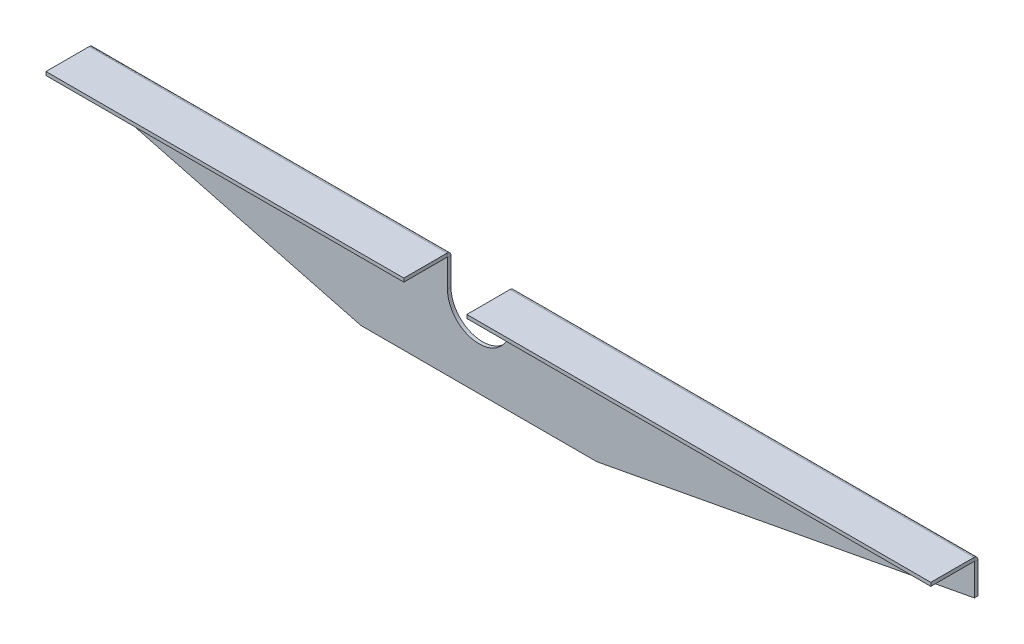
SolidWorks part; units mm, degrees
note: The reader was unsure of these and kept them because the rebuilt part matched: flange length of "Edge-Flange1".
material "Galvanized Steel"
ref_plane "Front Plane" through (0, 0, 0) normal (0, 0, 1) x (1, 0, 0)
ref_plane "Top Plane" through (0, 0, 0) normal (0, 1, 0) x (1, 0, 0)
ref_plane "Right Plane" through (0, 0, 0) normal (1, 0, 0) x (0, 0, -1)
sketch "Sketch1" plane through (0, 0, 0) normal (0, 0, 1) x (1, 0, 0)
  line L0 (13.35, 0) -> (13.35, 13.35)
  line L1 (13.35, 13.35) -> (210, 13.35)
  line L2 (210, 13.35) -> (210, -1.65)
  line L3 (210, -1.65) -> (50, -31.65)
  line L4 (50, -31.65) -> (-50, -31.65)
  line L5 (-50, -31.65) -> (-165, -1.65)
  line L6 (-165, -1.65) -> (-165, 13.35)
  line L7 (-165, 13.35) -> (-13.35, 13.35)
  line L8 (-13.35, 13.35) -> (-13.35, 0)
  arc A0 (-13.35, 0) -> (13.35, 0) centre (0, 0) ccw
  point P1 (0, -31.65)
  dimension "D1" = 26.7
  dimension "D2" = 100
  dimension "D3" = 0
  dimension "D4" = 15
  dimension "D5" = 15
  dimension "D6" = 165
  dimension "D7" = 210
  dimension "D8" = 45
base flange "Base-Flange1" sketch "Sketch1" thickness 1.5 reverse thickness direction no parameters "D1"=0.2
edge flange "Edge-Flange1" sketch "Sketch10" flange profiles "Sketch10", "Sketch11" flange angle 90 flange length 20 flange position material inside bend radius 0.2 thickness 1.5 relief rectangular parameters "D6"=10, "D8"=1
sketch "Sketch10" plane through (0, 13.35, 0) normal (0, 1, 0) x (-1, 0, 0)
  line L0 (13.35, 0) -> (165, 0) construction
  line L2 (13.35, 0) -> (13.35, 18.5)
  line L3 (13.35, 18.5) -> (165, 18.5)
  line L4 (165, 18.5) -> (165, 0)
  line L7 (13.35, 0) -> (165, 0)
sketch "Sketch11" plane through (0, 13.35, 0) normal (0, 1, 0) x (-1, 0, 0)
  line L0 (-210, 0) -> (-13.35, 0) construction
  line L2 (-210, 0) -> (-210, 18.5)
  line L3 (-210, 18.5) -> (-13.35, 18.5)
  line L4 (-13.35, 18.5) -> (-13.35, 0)
  line L7 (-210, 0) -> (-13.35, 0)
bend "EdgeBend1" bend radius 0.2 bend angle 90 parameters "D5"=1
bend "EdgeBend2" bend radius 0.2 bend angle 90 parameters "D5"=2
sketch "Bend-Lines1" [suppressed] plane through (0, 0, 0) normal (0, 1, 0) x (1, 0, 0)
sketch "Bounding-Box1" [suppressed] plane through (0, 0, 0) normal (0, 1, 0) x (1, 0, 0)
sheet metal parameters "Sheet-Metal1" thickness 1.5 parameters "D1"=0.2
flat pattern "Flat-Pattern1" [suppressed]
sketch "Bend-Lines2" plane through (0, 0, 0) normal (0, 1, 0) x (1, 0, 0)
sketch3d "Bounding-Box2" [suppressed]
  line L0 (350, -31.65, 0) -> (-350, -31.65, 0) construction
  line L1 (350, 13.35, 0) -> (-350, 13.35, 0) construction
  line L2 (350, -31.65, 0) -> (350, 13.35, 0) construction
  line L3 (-350, -31.65, 0) -> (-350, 13.35, 0) construction
sheet metal parameters "Sheet-Metal2" thickness 1.5 parameters "D1"=0.2
flat pattern "Flat-Pattern1"
sketch "Bend-Lines2" plane through (0, 0, 0) normal (0, 0, 1) x (1, 0, 0)
  line L0 (210, 12.3961) -> (13.35, 12.3961) construction
  line L1 (-13.35, 12.3961) -> (-165, 12.3961) construction
  line L2 (210, 12.3961) -> (13.35, 12.3961) construction
  line L3 (-13.35, 12.3961) -> (-165, 12.3961) construction
sketch3d "Bounding-Box2" [suppressed]
  line L0 (-165, -31.65, 0) -> (210, -31.65, 0) construction
  line L1 (-165, 31.4423, 0) -> (210, 31.4423, 0) construction
  line L2 (-165, -31.65, 0) -> (-165, 31.4423, 0) construction
  line L3 (210, -31.65, 0) -> (210, 31.4423, 0) construction
bend of the flat pattern "Flatten-<EdgeBend1>1"
bend of the flat pattern "Flatten-<EdgeBend2>1"
